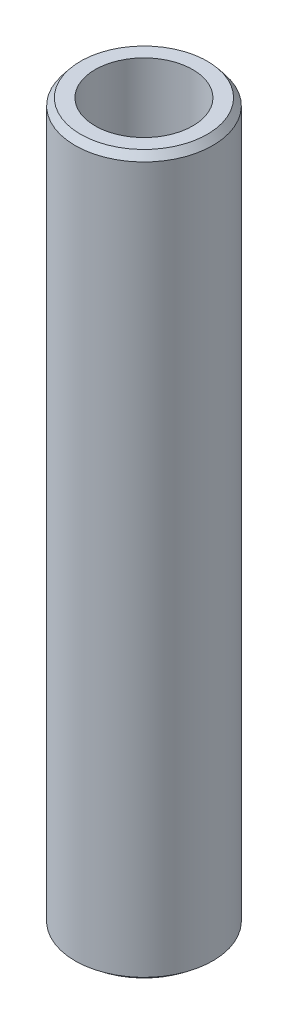
SolidWorks part; units mm, degrees
ref_plane "Front Plane" through (0, 0, 0) normal (0, 0, 1) x (1, 0, 0)
ref_plane "Top Plane" through (0, 0, 0) normal (0, 1, 0) x (1, 0, 0)
ref_plane "Right Plane" through (0, 0, 0) normal (1, 0, 0) x (0, 0, -1)
sketch "Sketch1" plane through (0, 0, 0) normal (0, 1, 0) x (1, 0, 0)
  circle A0 centre (0, 0) radius 57.5
  dimension "SHAFT_OD" = 115
extrude "Boss-Extrude1" add sketch "Sketch1" along normal blind 600
sketch "Sketch2" plane through (0, 0, 0) normal (0, 1, 0) x (1, 0, 0)
  circle A0 centre (0, 0) radius 40.7664
  dimension "BORE_D" = 81.5328
extrude "Cut-Extrude1" cut sketch "Sketch2" along normal through all
chamfer "Chamfer1" distance 5.8102 angle 38.289 2 edges at (0, 600, 57.5) (0, 0, 57.5) first distance on face at (0, 600, 57.5) first distance on face at (0, 0, 40.7664)
